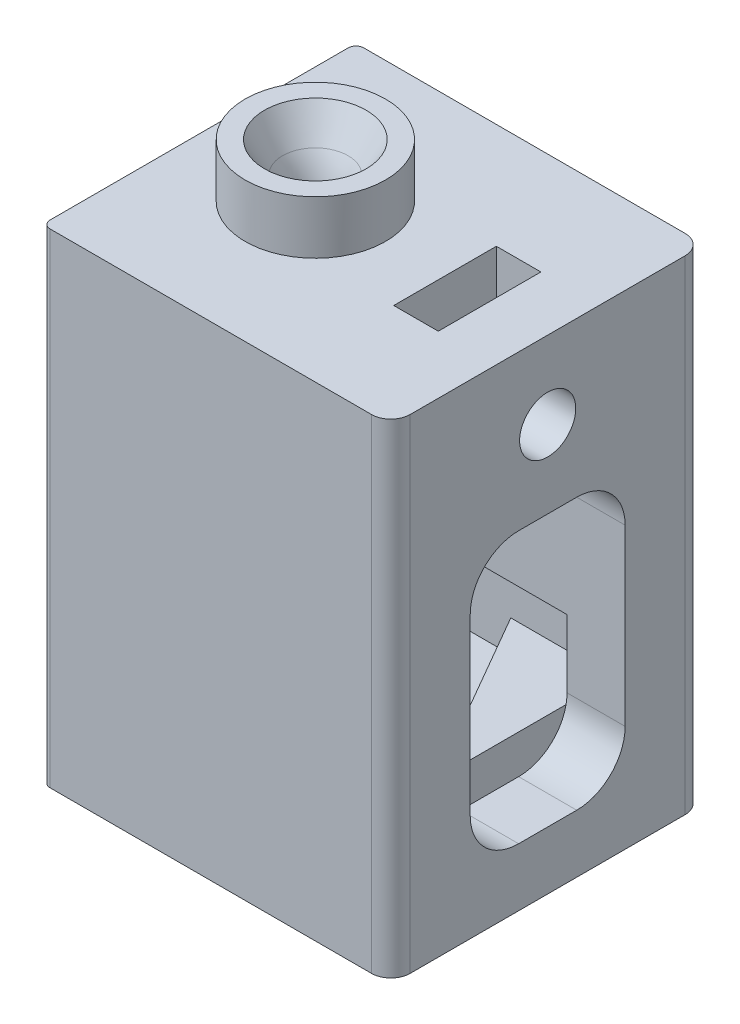
SolidWorks part; units mm, degrees
note: '?' marks a value the reader was unsure of.
ref_plane "Front Plane" through (0, 0, 0) normal (0, 0, 1) x (1, 0, 0)
ref_plane "Top Plane" through (0, 0, 0) normal (0, 1, 0) x (1, 0, 0)
ref_plane "Right Plane" through (0, 0, 0) normal (1, 0, 0) x (0, 0, -1)
sketch "Sketch1" plane through (0, 0, 0) normal (0, 1, 0) x (1, 0, 0)
  line L7 (-6, -6.5) -> (6, -6.5)
  line L8 (-6, -6.5) -> (-6, 6.5)
  line L9 (-6, 6.5) -> (6, 6.5)
  line L10 (6, -6.5) -> (6, 6.5)
  line L11 (-6, -6.5) -> (6, 6.5) construction
  line L12 (-6, 6.5) -> (6, -6.5) construction
  point P0 (0, 0)
  dimension "D1" = 12
  dimension "D3" = 13
extrude "Boss-Extrude1" add sketch "Sketch1" along normal blind 19
sketch "Sketch2" plane through (0, 0, 0) normal (0, -1, 0) x (1, 0, 0)
  circle A0 centre (0, 0) radius 4
  dimension "D1" = 8
extrude "Cut-Extrude1" cut sketch "Sketch2" against normal blind 16
ref_plane "Plane1" through (0, 2, 0) normal (0, -1, 0) x (-1, 0, 0)
sketch "Sketch3" plane through (0, 0, 0) normal (0, -1, 0) x (1, 0, 0)
  line L1 (6, 6.5) -> (6, -6.5) construction
  line L6 (6, -6.5) -> (-6, -6.5) construction
  line L10 (-6, -6.5) -> (-6, 6.5) construction
  line L11 (-6, 6.5) -> (6, 6.5) construction
  line L12 (6, 6.5) -> (6, -6.5)
  line L13 (6, -6.5) -> (-6, -6.5)
  line L14 (-6, -6.5) -> (-6, 6.5)
  line L15 (-6, 6.5) -> (6, 6.5)
extrude "Cut-Extrude2" cut sketch "Sketch3" against normal blind 6 from surface at -2 starting at plane "Plane1"
sketch "Sketch5" plane through (0, 19, 0) normal (0, 1, 0) x (1, 0, 0)
  line L0 (6, -6.5) -> (6, 6.5) construction
  line L1 (-6, -6.5) -> (6, -6.5)
  line L2 (-6, -6.5) -> (-6, 6.5)
  line L3 (-6, 6.5) -> (6, 6.5)
  line L4 (6, -6.5) -> (6, 6.5)
  line L5 (6, 6.5) -> (-6, 6.5) construction
extrude "Boss-Extrude2" add sketch "Sketch5" along normal blind 5
sketch "Sketch9" plane through (0, 24, 0) normal (0, 1, 0) x (1, 0, 0)
  circle A0 centre (0, 0) radius 1
  dimension "D1" = 2
fillet "Fillet1" radius 2 2 edges at (-6, 16, 6.5) (-6, 16, -6.5)
fillet "Fillet4" radius 2 2 edges at (-6, 1, -6.5) (-6, 1, 6.5)
ref_plane "Plane4" through (0, 0, 0) normal (0, 0, 1) x (1, 0, 0)
sketch "Sketch21" plane through (-6, 0, 0) normal (-1, 0, 0) x (0, 0, 1)
  line L0 (-4.5, 24) -> (-4.5, 8) construction
  line L1 (-4.5, 22) -> (-2, 22)
  line L2 (-4.5, 22) -> (-4.5, 14)
  line L3 (-4.5, 14) -> (-2, 14)
  line L4 (-2, 22) -> (-2, 14)
  line L5 (-4.5, 24) -> (4.5, 24) construction
  line L6 (0, 24) -> (0, 0) construction
  line L7 (-4.5, 0) -> (4.5, 0) construction
  line L8 (2, 22) -> (2, 14)
  line L9 (4.5, 14) -> (2, 14)
  line L10 (4.5, 22) -> (4.5, 14)
  line L11 (4.5, 22) -> (2, 22)
  line L12 (4.5, 8) -> (4.5, 24) construction
  line L13 (-4.5, 0) -> (4.5, 0)
  line L14 (-4.5, 0) -> (-4.5, 1.5)
  line L15 (-4.5, 1.5) -> (4.5, 1.5)
  line L16 (4.5, 0) -> (4.5, 1.5)
  line L17 (-4.5, 2) -> (-4.5, 0) construction
  line L18 (-4.5, 0) -> (4.5, 0) construction
  dimension "D1" = 2.5
  dimension "D2" = 2
  dimension "D3" = 8
  dimension "D4" = 1.5
extrude "Boss-Extrude4" add sketch "Sketch21" along normal blind 1
fillet "Fillet3" radius 0.5 4 edges at (-7, 22, 3.25) (-7, 18, 2) (-7, 14, 3.25) (-7, 18, 4.5)
fillet "Fillet7" radius 0.5 4 edges at (-7, 14, -3.25) (-7, 18, -4.5) (-7, 18, -2) (-7, 22, -3.25)
fillet "Fillet5" radius 0.5 2 edges at (-7, 0.75, -4.5) (-7, 0.75, 4.5)
sketch "Sketch23" plane through (0, 0, 0) normal (0, -1, 0) x (1, 0, 0)
  line L4 (-7, 4) -> (-7, -4)
  line L8 (-4, -6.5) -> (6, -6.5)
  line L9 (6, -6.5) -> (6, 6.5)
  line L10 (6, 6.5) -> (-4, 6.5)
  line L11 (-7, 4) -> (-7, -4)
  line L14 (-4, -6.5) -> (6, -6.5)
  line L15 (6, -6.5) -> (6, 6.5)
  line L16 (6, 6.5) -> (-4, 6.5)
  line L18 (-6.5, -4.5) -> (-6, -4.5)
  line L19 (-6.5, -4.5) -> (-6, -4.5)
  line L20 (-6, 4.5) -> (-6.5, 4.5)
  line L21 (-6, 4.5) -> (-6.5, 4.5)
  circle A0 centre (0, 0) radius 4 construction
  circle A1 centre (0, 0) radius 4
  arc A5 (-7, -4) -> (-6.5, -4.5) centre (-6.5, -4) ccw
  arc A6 (-7, -4) -> (-6.5, -4.5) centre (-6.5, -4) ccw
  arc A12 (-6, -4.5) -> (-4, -6.5) centre (-4, -4.5) ccw
  arc A22 (-6, -4.5) -> (-4, -6.5) centre (-4, -4.5) ccw
  arc A24 (-4, 6.5) -> (-6, 4.5) centre (-4, 4.5) ccw
  arc A25 (-4, 6.5) -> (-6, 4.5) centre (-4, 4.5) ccw
  arc A26 (-6.5, 4.5) -> (-7, 4) centre (-6.5, 4) ccw
  arc A27 (-6.5, 4.5) -> (-7, 4) centre (-6.5, 4) ccw
  dimension "D1" = 0
extrude "Boss-Extrude5" add sketch "Sketch23" along normal blind 1
sketch "Sketch25" plane through (6, 0, 0) normal (1, 0, 0) x (0, 0, -1)
  line L0 (6.5, 24) -> (6.5, 8) construction
  line L1 (-6.5, 8) -> (6.5, 8)
  line L2 (-6.5, 8) -> (-6.5, 11)
  line L3 (-6.5, 11) -> (6.5, 11)
  line L4 (6.5, 8) -> (6.5, 11)
  dimension "D1" = 3
sketch "Sketch26" plane through (0, 0, -6.5) normal (0, 0, -1) x (-1, 0, 0)
  line L0 (-6, 24) -> (-12, 24)
  line L3 (-12, 24) -> (-12, -1)
  line L4 (-12, -1) -> (-6, -1)
  line L5 (-6, -1) -> (-6, 2)
  line L6 (-6, 2) -> (-9, 2)
  line L7 (-9, 2) -> (-9, 8)
  line L8 (-9, 8) -> (-6, 8)
  line L9 (-6, 8) -> (-6, 11) construction
  line L10 (-6, 8) -> (-6, 11) construction
  line L11 (-6, 8) -> (-6, 24)
  line L12 (-6, 8) -> (4, 8) construction
  dimension "D2" = 3
  dimension "D3" = 3
extrude "Boss-Extrude6" add sketch "Sketch26" against normal through all
sketch "Sketch30" plane through (0, 24, 0) normal (0, 1, 0) x (1, 0, 0)
  line L0 (-6, 4.5) -> (-6, 8.1)
  line L1 (-6, 8.1) -> (12, 8.1)
  line L2 (12, 8.1) -> (12, 6.5)
  line L3 (12, 6.5) -> (-4, 6.5)
  line L5 (-4, 6.5) -> (-6, 6.5)
  line L6 (-10.45, 0) -> (10.45, 0) construction
  line L7 (-4, -6.5) -> (-6, -6.5)
  line L8 (12, -6.5) -> (-4, -6.5)
  line L9 (12, -8.1) -> (12, -6.5)
  line L10 (-6, -8.1) -> (12, -8.1)
  line L11 (-6, -4.5) -> (-6, -8.1)
  line L12 (12, -6.5) -> (12, 6.5) construction
  arc A0 (-4, 6.5) -> (-6, 4.5) centre (-4, 4.5) ccw construction
  arc A1 (-4, 6.5) -> (-6, 4.5) centre (-4, 4.5) ccw
  arc A2 (-4, -6.5) -> (-6, -4.5) centre (-4, -4.5) cw
  dimension "D1" = 1.6
extrude "Boss-Extrude7" add sketch "Sketch30" against normal through all
sketch "Sketch11" plane through (0, 24, 0) normal (0, 1, 0) x (1, 0, 0)
  line L0 (9, 0) -> (6.7, 0) construction
  line L1 (9, 2.65) -> (6.7, 2.65)
  line L2 (9, 2.65) -> (9, -2.65)
  line L3 (9, -2.65) -> (6.7, -2.65)
  line L4 (6.7, 2.65) -> (6.7, -2.65)
  line L5 (9, 0) -> (-6, 0) construction
  line L7 (-6, 8.1) -> (-6, -8.1) construction
  line L9 (12, -8.1) -> (12, 8.1) construction
  dimension "D1" = 5.3
  dimension "D2" = 2.3
  dimension "D3" = 3
extrude "Cut-Extrude4" cut sketch "Sketch11" against normal blind 7
sketch "Sketch34" plane through (-6, 0, 0) normal (-1, 0, 0) x (0, 0, 1)
  line L0 (4.5, 2) -> (-4.5, 2) construction
  line L1 (-6.75, 8) -> (6.75, 8)
  line L2 (-6.75, 8) -> (-6.75, 2)
  line L3 (-6.75, 2) -> (6.75, 2)
  line L4 (6.75, 8) -> (6.75, 2)
  line L5 (0, 2) -> (0, 8) construction
  line L6 (-6.75, 5) -> (6.75, 5) construction
  line L7 (4.5, 8) -> (-4.5, 8) construction
  point P0 (0, 5)
  dimension "D1" = 13.5
extrude "Cut-Extrude5" cut sketch "Sketch34" against normal up to surface (15 mm away) up to face at (9, 5, 0)
hole_wizard "M2.5 Clearance Hole1" positions "Sketch32" profile "Sketch33" hole size "M2.5" standard "ANSI Metric"
sketch "Sketch32" plane through (12, 0, 0) normal (1, 0, 0) x (0, 0, -1)
  line L0 (-8.1, 24) -> (8.1, 24) construction
  point P0 (0, 20)
  dimension "D1" = 4
sketch "Sketch33" plane through (12, 20, 0) normal (0, 1, 0) x (0, 0, -1)
  line L0 (0, 0) -> (0, 14.25)
  line L1 (0, 14.25) -> (1.45, 13.3788)
  line L2 (1.45, 13.3788) -> (1.45, 0)
  line L5 (1.45, 0) -> (0, 0)
  line L10 (0, 14.25) -> (-1.45, 13.3788) construction
  line L11 (0, -6.35) -> (0, 107.95) construction
  dimension "Hole Dia." = 2.9
  dimension "Hole Depth" = 14.25
  dimension "Drill Angle" = 118
fillet "Fillet8" radius 0.4 4 edges at (-6, 11.5, -8.1) (-6, 11.5, 8.1) (-6, 5, -6.75) (-6, 5, 6.75)
sketch "Sketch31" plane through (0, 24, 0) normal (0, 1, 0) x (1, 0, 0)
  circle A0 centre (0, 0) radius 3.625
  circle A1 centre (0, 0) radius 2.625
  dimension "D1" = 7.25
  dimension "D2" = 1
extrude "Boss-Extrude8" add sketch "Sketch31" along normal blind 2.75
fillet "Fillet9" radius 1 2 edges at (12, 11.5, 8.1) (12, 11.5, -8.1)
extrude "Cut-Extrude6" cut sketch "Sketch9" against normal through all contours A0
sketch "Sketch42" plane through (12, 0, 0) normal (1, 0, 0) x (0, 0, -1)
  line L0 (-1.5, 13.5) -> (1.5, 13.5) construction
  line L1 (-1.5, 16) -> (1.5, 16)
  line L2 (-1.5, 11) -> (1.5, 11) construction
  line L3 (-4, 13.5) -> (-4, 4.5)
  line L4 (-1.5, 2) -> (1.5, 2)
  line L5 (4, 4.5) -> (4, 13.5)
  arc A0 (-1.5, 16) -> (-4, 13.5) centre (-1.5, 13.5) ccw
  arc A1 (4, 13.5) -> (1.5, 16) centre (1.5, 13.5) ccw
  arc A2 (-4, 4.5) -> (-1.5, 2) centre (-1.5, 4.5) ccw
  arc A3 (1.5, 2) -> (4, 4.5) centre (1.5, 4.5) ccw
  arc A4 (-4, 13.5) -> (-1.5, 11) centre (-1.5, 13.5) ccw construction
  arc A5 (1.5, 11) -> (4, 13.5) centre (1.5, 13.5) ccw construction
  point P18 (0, 13.5)
  point P21 (0, 11)
  dimension "D3" = 2.5
  dimension "D4" = 2.5
  dimension "D5" = 2.5
  dimension "D1" = 3
  dimension "D6" = 14
  dimension "D7" = 6.5
extrude "Cut-Extrude8" cut sketch "Sketch42" against normal blind 12
ref_plane "Plane6" through (0, 0, 0) normal (0, 0, 1) x (1, 0, 0)
sketch "Sketch43" plane through (0, 0, 0) normal (0, 0, 1) x (1, 0, 0)
  line L0 (1, 24) -> (2.625, 26.75)
  line L1 (-5.6, 24) -> (11, 24) construction
  line L2 (2.625, 26.75) -> (2.625, 24)
  line L3 (2.625, 24) -> (1, 24)
  line L4 (2.625, 26.75) -> (-2.625, 26.75) construction
  line L5 (3.625, 26.75) -> (-3.625, 26.75) construction
  line L6 (3.625, 24) -> (3.625, 26.75) construction
  dimension "D1" = 1
ref_axis "Axis1" through (0, 26.75, 0) along (0, -1, 0)?
ref_plane "Plane7" through (0, 0, 0) normal (-1, 0, 0) x (0, -1, 0)
ref_plane "Plane8" through (0, 0, 0) normal (-0.7071, 0, -0.7071) x (-0.7071, 0, 0.7071)
ref_axis "Axis3" through (0, 28.9875, 0) along (0, -1, 0)
revolve "Revolve1" add sketch "Sketch43" angle 360 about axis through (0, 28.9875, 0) along (0, -1, 0)
fillet "Fillet10" radius 5 1 edges at (0, 24, 1)
ref_plane "Plane9" through (0, 2, 0) normal (0, 1, 0) x (1, 0, 0)
sketch "Sketch45" plane through (0, 2, 0) normal (0, 1, 0) x (1, 0, 0)
  line L0 (-5.6, 8.1) -> (11, 8.1) construction
  line L1 (-5.5426, 3.2) -> (-7.3901, 0) construction
  line L2 (-5.5426, -3.2) -> (-3.695, -6.4) construction
  line L3 (-3.695, -6.4) -> (0, -6.4) construction
  line L4 (3.695, -6.4) -> (7.3901, 0)
  line L5 (7.3901, 0) -> (3.695, 6.4)
  line L6 (0, 6.4) -> (-3.695, 6.4) construction
  line L8 (3.695, -6.4) -> (9, -6.4)
  line L9 (9, -6.4) -> (9, 6.4)
  line L10 (9, 6.4) -> (3.695, 6.4)
  line L11 (9, -6.75) -> (9, -1.5) construction
  line L12 (3.695, 6.4) -> (0, 6.4) construction
  line L13 (0, -6.4) -> (3.695, -6.4) construction
  line L14 (-3.695, 6.4) -> (-5.5426, 3.2) construction
  line L15 (-7.3901, 0) -> (-5.5426, -3.2) construction
  arc A0 (-5.5426, 3.2) -> (-5.5426, -3.2) centre (0, 0) ccw construction
  arc A1 (5.5426, 3.2) -> (0, 6.4) centre (0, 0) ccw construction
  arc A2 (0, -6.4) -> (5.5426, -3.2) centre (0, 0) ccw construction
  arc A3 (5.5426, -3.2) -> (5.5426, 3.2) centre (0, 0) ccw construction
  arc A4 (-5.5426, -3.2) -> (0, -6.4) centre (0, 0) ccw construction
  arc A5 (0, 6.4) -> (-5.5426, 3.2) centre (0, 0) ccw construction
  dimension "D1" = 12.8
extrude "Boss-Extrude9" add sketch "Sketch45" along normal blind 2
